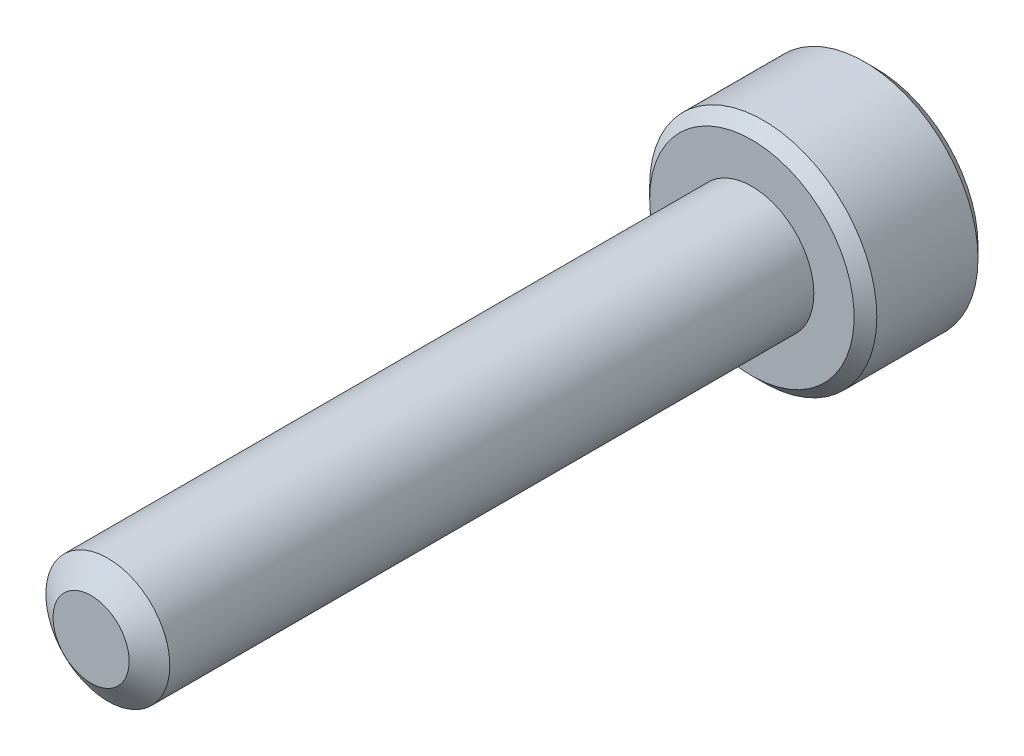
SolidWorks part; units mm, degrees
other "DetailItem1"
material "1.4310 (X10CrNi18-8)"
ref_plane "Front Plane" through (0, 0, 0) normal (0, 0, 1) x (1, 0, 0)
ref_plane "Top Plane" through (0, 0, 0) normal (0, 1, 0) x (1, 0, 0)
ref_plane "Right Plane" through (0, 0, 0) normal (1, 0, 0) x (0, 0, -1)
sketch "Sketch1" plane through (0, 0, 0) normal (0, 0, 1) x (1, 0, 0)
  circle A0 centre (0, 0) radius 1.5
  dimension "OD" = 3
extrude "Extrude1" add sketch "Sketch1" against normal blind 16
sketch "Sketch2" plane through (0, 0, 0) normal (0, 0, 1) x (1, 0, 0)
  circle A0 centre (0, 0) radius 1.5 construction
  circle A1 centre (0, 0) radius 1.5
curve "Helix/Spiral1" pitch 0.5 height 16.5 turns 33 parameters "pitch"=0.5
sketch "Sketch3" plane through (0, 0, 0) normal (1, 0, 0) x (0, 0, -1)
  line L0 (-0.4375, 1.5) -> (-0.25, 1.1752)
  line L1 (-0.25, 1.1752) -> (-0.1875, 1.1752)
  line L2 (-0.1875, 1.1752) -> (0, 1.5)
  line L3 (-0.4375, 1.5) -> (0, 1.5)
  line L4 (-0.2187, 1.5) -> (-0.2188, 1.1752) construction
  line L5 (-0.3438, 1.3376) -> (-0.0938, 1.3376) construction
  line L6 (0, 1.5) -> (0, -1.5) construction
  dimension "D1" = 0.0625
  dimension "D2" = 0.25
  dimension "D3" = 60
sweep "Cut-Sweep1" [suppressed] cut profiles "Sketch3" path "Helix/Spiral1"
sketch "Sketch4" plane through (0, 0, 0) normal (1, 0, 0) x (0, 0, -1)
  line L0 (0.4053, 1.5) -> (0, 0.9212)
  line L1 (0, 0.9212) -> (0, 1.5)
  line L2 (0.4053, 1.5) -> (0, 1.5)
  line L3 (-0.4375, 1.5) -> (0, 1.5) construction
  line L4 (0, 0) -> (7.0209, 0) construction
  dimension "D1" = 55
  dimension "D2" = 0.254
revolve "Cut-Revolve1" cut sketch "Sketch4" angle 360 about L4
sketch "Sketch6" plane through (0, 0, -16) normal (0, 0, -1) x (-1, 0, 0)
  circle A0 centre (0, 0) radius 2.75
  dimension "head dia" = 5.5
extrude "Extrude2" add sketch "Sketch6" along normal blind 3
sketch "Sketch7" plane through (0, 0, -19) normal (0, 0, -1) x (-1, 0, 0)
  line L1 (0, 1.4434) -> (-1.25, 0.7217)
  line L2 (-1.25, 0.7217) -> (-1.25, -0.7217)
  line L3 (-1.25, -0.7217) -> (0, -1.4434)
  line L4 (0, -1.4434) -> (1.25, -0.7217)
  line L5 (1.25, -0.7217) -> (1.25, 0.7217)
  line L6 (1.25, 0.7217) -> (0, 1.4434)
  circle A0 centre (0, 0) radius 1.25 construction
  dimension "hex dia" = 2.5
extrude "Cut-Extrude1" cut sketch "Sketch7" against normal blind 1.875
sketch "Sketch8" plane through (0, 0, -19) normal (0, 0, -1) x (-1, 0, 0)
  circle A0 centre (0, 0) radius 1.4434
extrude "Cut-Extrude2" cut sketch "Sketch8" against normal through all draft 45
chamfer "Chamfer1" distance 0.275 angle 45 2 edges at (-2.75, 0, -19) (-2.75, 0, -16)
sketch "Sketch10" plane through (0, 0, -16) normal (0, 0, 1) x (1, 0, 0)
  circle A1 centre (0, 0) radius 1.5
  circle A2 centre (0, 0) radius 1.5
  dimension "D1" = 0
ref_plane "Plane1" through (0, 0, 0) normal (0, 0, 1) x (1, 0, 0)
extrude "partial thread" [suppressed] add sketch "Sketch10" along normal up to surface (4 mm away) separate body up to plane "Plane1"
chamfer "Chamfer2" [suppressed] distance 0.06 angle 45
combine bodies "Combine1" [suppressed] operation type add bodies to combine 107 108
sketch "Sketch9" plane through (0, 0, 0) normal (1, 0, 0) x (0, 0, -1)
  line L0 (0, 1.5) -> (0, -1.5) construction
  line L1 (1.25, 1.5) -> (1.25, -1.5) construction
  dimension "D1" = 1.25
equation "\"D3@Helix/Spiral1\" = \"screw length@Extrude1\"+\"pitch@Helix/Spiral1\""
equation "\"D1@Sketch3\" = \"pitch@Helix/Spiral1\"*.125"
equation "\"D2@Sketch3\" = \"pitch@Helix/Spiral1\"*.5"
equation "\"D1@Cut-Extrude1\" = \"hex dia@Sketch7\"*.75"
equation "\"D1@Chamfer1\" = \"head dia@Sketch6\"*.05"
equation "\"D1@Sketch9\" = \"pitch@Helix/Spiral1\"*2.5"
equation "\"D1@Chamfer2\"=\"OD@Sketch1\"*.02"
